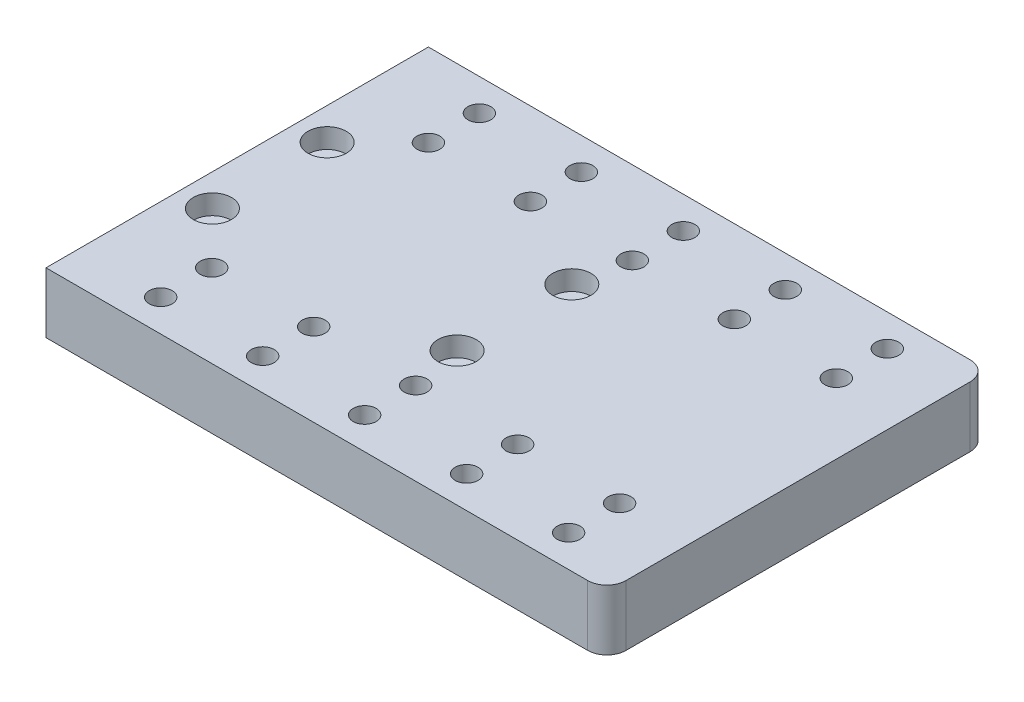
SolidWorks part; units mm, degrees
ref_plane "前视基准面" through (0, 0, 0) normal (0, 0, 1) x (1, 0, 0)
ref_plane "上视基准面" through (0, 0, 0) normal (0, 1, 0) x (1, 0, 0)
ref_plane "右视基准面" through (0, 0, 0) normal (1, 0, 0) x (0, 0, -1)
sketch "草图1" plane through (0, 0, 0) normal (0, 1, 0) x (1, 0, 0)
  line L1 (-44, 30) -> (44, 30)
  line L2 (-44, 30) -> (-44, -30)
  line L3 (-44, -30) -> (44, -30)
  line L4 (44, 30) -> (44, -30)
  line L5 (-44, 30) -> (44, -30) construction
  line L6 (-44, -30) -> (44, 30) construction
  point P0 (0, 0)
  dimension "D1" = 60
  dimension "D2" = 88
extrude "凸台-拉伸1" add sketch "草图1" along normal blind 9.5
fillet "圆角1" radius 3 2 edges at (44, 4.75, -30) (44, 4.75, 30)
sketch "草图2" plane through (0, 9.5, 0) normal (0, 1, 0) x (1, 0, 0)
  line L0 (-44, 30) -> (-44, -30) construction
  circle A0 centre (-39, -8.8898) radius 1.3
  circle A1 centre (-39, 9.1102) radius 1.3
  circle A2 centre (-0.5, 9) radius 1.3
  circle A3 centre (-0.5, -9) radius 1.3
  dimension "D1" = 2.6
  dimension "D2" = 5
  dimension "D3" = 2.6
extrude "切除-拉伸1" cut sketch "草图2" against normal through all
sketch "草图3" plane through (0, 9.5, 0) normal (0, 1, 0) x (1, 0, 0)
  circle A0 centre (-39, -8.8898) radius 3
  circle A1 centre (-39, 9.1102) radius 3
  circle A2 centre (-0.5, -9) radius 3
  circle A3 centre (-0.5, 9) radius 3
  dimension "D1" = 6
extrude "切除-拉伸2" cut sketch "草图3" against normal blind 3.1
sketch "草图4" plane through (0, 9.5, 0) normal (0, 1, 0) x (1, 0, 0)
  line L0 (-44, -30) -> (41, -30) construction
  line L1 (41, 30) -> (-44, 30) construction
  line L2 (44, -27) -> (44, 27) construction
  circle A0 centre (-31, -25) radius 1.8
  circle A1 centre (-31, 25) radius 1.8
  circle A2 centre (-31, -17) radius 1.8
  circle A3 centre (-31, 17) radius 1.8
  dimension "D1" = 3.6
  dimension "D2" = 5
  dimension "D3" = 5
  dimension "D4" = 75
  dimension "D5" = 8
  dimension "D6" = 8
  dimension "D7" = 75
  dimension "D8" = 75
  dimension "D9" = 75
extrude "切除-拉伸3" cut sketch "草图4" against normal through all
pattern_linear "阵列(线性)1" count 5 spacing 16 along (1, 0, 0) of "切除-拉伸3"
